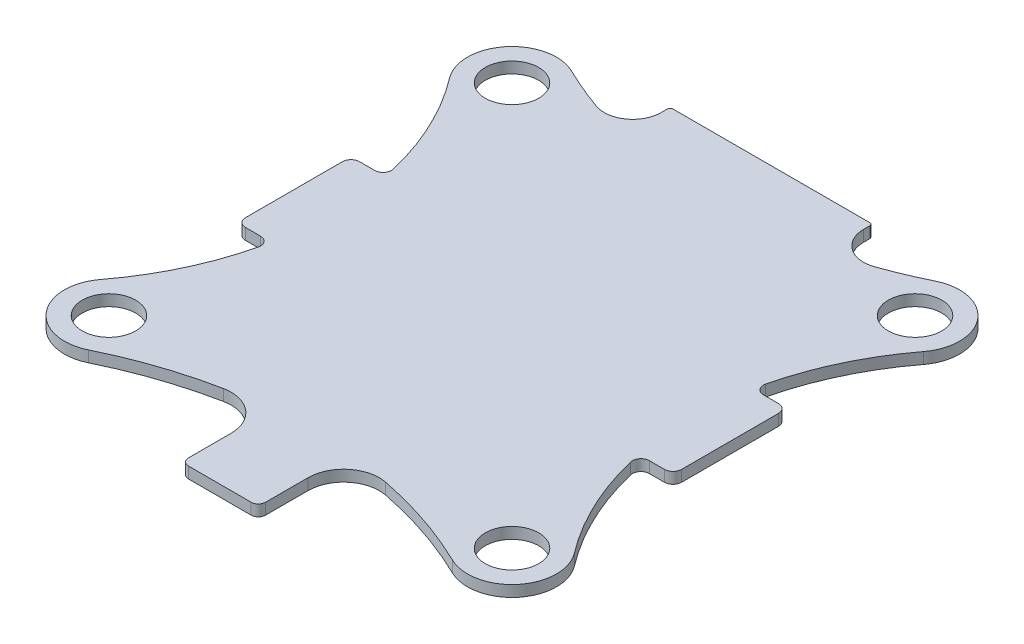
SolidWorks part; units mm, degrees
ref_plane "Front Plane" through (0, 0, 0) normal (0, 0, 1) x (1, 0, 0)
ref_plane "Top Plane" through (0, 0, 0) normal (0, 1, 0) x (1, 0, 0)
ref_plane "Right Plane" through (0, 0, 0) normal (1, 0, 0) x (0, 0, -1)
sketch "Sketch1" plane through (0, 0, 0) normal (0, 1, 0) x (1, 0, 0)
  line L0 (-17.9605, 17.9605) -> (17.9605, -17.9605) construction
  line L1 (-15.875, -17.78) -> (15.875, -17.78) construction
  line L2 (-15.875, -17.78) -> (-15.875, 17.78) construction
  line L3 (-15.875, 17.78) -> (15.875, 17.78) construction
  line L4 (15.875, -17.78) -> (15.875, 17.78) construction
  line L5 (-17.9605, -17.9605) -> (17.9605, 17.9605) construction
  line L6 (-20.7668, -15.1542) -> (-15.1542, -20.7668) construction
  line L7 (0, -17.78) -> (0, 17.78) construction
  line L8 (-15.875, 0) -> (15.875, 0) construction
  line L9 (20.7668, -15.1542) -> (15.1542, -20.7668) construction
  line L10 (-20.7668, 15.1542) -> (-15.1542, 20.7668) construction
  line L11 (20.7668, 15.1542) -> (15.1542, 20.7668) construction
  line L12 (-17.331, -5.08) -> (-18.669, -5.08)
  line L13 (-19.431, -4.318) -> (-19.431, 4.318)
  line L14 (-18.669, 5.08) -> (-17.331, 5.08)
  line L15 (18.669, 5.08) -> (17.331, 5.08)
  line L16 (19.431, -4.318) -> (19.431, 4.318)
  line L17 (-3.429, -21.6064) -> (-3.429, -25.4)
  line L18 (-2.794, -26.035) -> (2.794, -26.035)
  line L19 (3.429, -25.4) -> (3.429, -21.6064)
  line L20 (-9.017, 22.3171) -> (-9.017, 22.86)
  line L21 (-8.763, 23.114) -> (8.763, 23.114)
  line L22 (9.017, 22.86) -> (9.017, 22.3171)
  line L28 (17.331, -5.08) -> (18.669, -5.08)
  circle A0 centre (-17.9605, -17.9605) radius 3.9688 construction
  circle A1 centre (17.9605, -17.9605) radius 3.9688 construction
  circle A2 centre (17.9605, 17.9605) radius 3.9688 construction
  circle A3 centre (-17.9605, 17.9605) radius 3.9688 construction
  arc A4 (-21.1194, 15.5579) -> (-21.1194, -15.5579) centre (-41.5741, 0) cw construction
  arc A5 (-16.2197, 21.5271) -> (16.2197, 21.5271) centre (0, 54.7579) ccw construction
  arc A6 (-16.2197, -21.5271) -> (16.2197, -21.5271) centre (0, -54.7579) cw construction
  arc A7 (21.1194, 15.5579) -> (21.1194, -15.5579) centre (41.5741, 0) ccw construction
  arc A8 (-21.1194, 15.5579) -> (-16.2197, 21.5271) centre (-17.9605, 17.9605) cw
  arc A9 (16.2197, 21.5271) -> (21.1194, 15.5579) centre (17.9605, 17.9605) cw
  arc A10 (21.1194, -15.5579) -> (16.2197, -21.5271) centre (17.9605, -17.9605) cw
  arc A11 (-21.1194, -15.5579) -> (-16.2197, -21.5271) centre (-17.9605, -17.9605) ccw
  circle A12 centre (-17.9605, -17.9605) radius 2.3813
  circle A13 centre (17.9605, -17.9605) radius 2.3813
  circle A14 centre (17.9605, 17.9605) radius 2.3813
  circle A15 centre (-17.9605, 17.9605) radius 2.3813
  arc A16 (-21.1194, -15.5579) -> (-16.5902, -6.0205) centre (-41.5741, 0) ccw
  arc A17 (-17.331, -5.08) -> (-16.5902, -6.0205) centre (-17.331, -5.842) cw
  arc A18 (-21.1194, 15.5579) -> (-16.5902, 6.0205) centre (-41.5741, 0) cw
  arc A19 (-16.5902, 6.0205) -> (-17.331, 5.08) centre (-17.331, 5.842) cw
  arc A20 (-18.669, 5.08) -> (-19.431, 4.318) centre (-18.669, 4.318) ccw
  arc A21 (-19.431, -4.318) -> (-18.669, -5.08) centre (-18.669, -4.318) ccw
  arc A22 (16.5902, 6.0205) -> (17.331, 5.08) centre (17.331, 5.842) ccw
  arc A23 (21.1194, 15.5579) -> (16.5902, 6.0205) centre (41.5741, 0) ccw
  arc A24 (21.1194, -15.5579) -> (16.5902, -6.0205) centre (41.5741, 0) cw
  arc A25 (17.331, -5.08) -> (16.5902, -6.0205) centre (17.331, -5.842) ccw
  arc A26 (19.431, -4.318) -> (18.669, -5.08) centre (18.669, -4.318) cw
  arc A27 (18.669, 5.08) -> (19.431, 4.318) centre (18.669, 4.318) cw
  arc A28 (-16.2197, -21.5271) -> (-7.2243, -18.4926) centre (0, -54.7579) cw
  arc A29 (16.2197, -21.5271) -> (7.2243, -18.4926) centre (0, -54.7579) ccw
  arc A30 (-7.2243, -18.4926) -> (-3.429, -21.6064) centre (-6.604, -21.6064) cw
  arc A31 (7.2243, -18.4926) -> (3.429, -21.6064) centre (6.604, -21.6064) ccw
  arc A32 (-3.429, -25.4) -> (-2.794, -26.035) centre (-2.794, -25.4) ccw
  arc A33 (3.429, -25.4) -> (2.794, -26.035) centre (2.794, -25.4) cw
  arc A34 (-16.2197, 21.5271) -> (-12.4094, 19.9244) centre (0, 54.7579) ccw
  arc A35 (16.2197, 21.5271) -> (12.4094, 19.9244) centre (0, 54.7579) cw
  arc A36 (-9.017, 22.3171) -> (-12.4094, 19.9244) centre (-11.557, 22.3171) cw
  arc A37 (9.017, 22.3171) -> (12.4094, 19.9244) centre (11.557, 22.3171) ccw
  arc A38 (-8.763, 23.114) -> (-9.017, 22.86) centre (-8.763, 22.86) ccw
  arc A39 (8.763, 23.114) -> (9.017, 22.86) centre (8.763, 22.86) cw
  point P4 (0, 17.78)
  point P6 (15.875, 0)
  point P11 (0, 0)
  point P12 (0, 0)
  point P19 (-17.9605, -17.9605)
  point P60 (-19.431, 5.08)
  point P63 (-19.431, -5.08)
  point P72 (19.431, -5.08)
  point P73 (19.431, 5.08)
  point P82 (3.429, -17.9393)
  point P85 (-3.429, -26.035)
  point P88 (3.429, -26.035)
  point P95 (-9.017, 18.8962)
  point P98 (9.017, 18.8962)
  point P102 (-9.017, 23.114)
  point P105 (9.017, 23.114)
  dimension "D3" = 7.9375
  dimension "D8" = 0.762
  dimension "D9" = 0.762
  dimension "D10" = 0.762
  dimension "D11" = 0.762
  dimension "D14" = 3.175
  dimension "D15" = 3.175
  dimension "D16" = 0.635
  dimension "D17" = 0.635
  dimension "D20" = 2.54
  dimension "D21" = 2.54
  dimension "D22" = 4.7625
  dimension "D23" = 0.254
  dimension "D24" = 0.254
  dimension "D1" = 31.75
  dimension "D2" = 35.56
  dimension "D4" = 50.8
  dimension "D5" = 3.556
  dimension "D6" = 5.08
  dimension "D7" = 5.08
  dimension "D12" = 6.858
  dimension "D13" = 8.255
  dimension "D18" = 5.334
  dimension "D19" = 18.034
extrude "Boss-Extrude2" add sketch "Sketch1" along normal blind 1 contours A12 | A13 | A14 | A15 | A28 A30 L17 A32 L18 A33 L19 A31 A29 A10 A24 A25 L28 A26 L16 A27 L15 A22 A23 A9 A35 A37 L22 A39 L21 A38 L20 A36 A34 A8 A18 A19 L14 A20 L13 A21 L12 A17 A16 A11 region at (-17.9605, 0, 17.9605) region at (17.9605, 0, 17.9605) region at (17.9605, 0, -17.9605) region at (-17.9605, 0, -17.9605)
